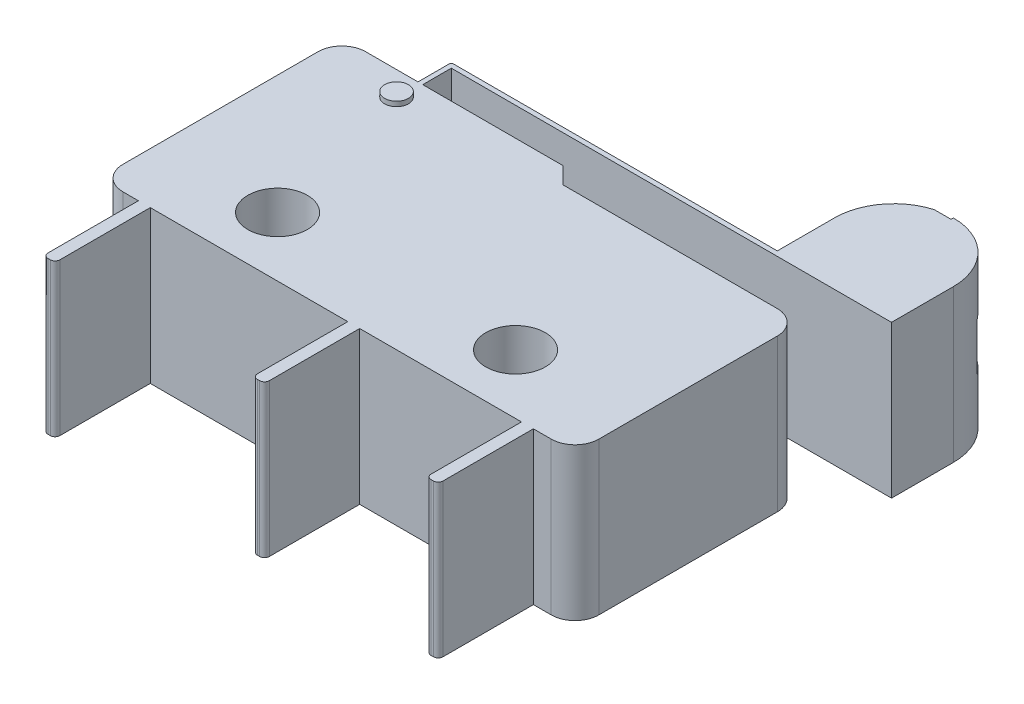
SolidWorks part; units mm, degrees
ref_plane "Front Plane" through (0, 0, 0) normal (0, 0, 1) x (1, 0, 0)
ref_plane "Top Plane" through (0, 0, 0) normal (0, 1, 0) x (1, 0, 0)
ref_plane "Right Plane" through (0, 0, 0) normal (1, 0, 0) x (0, 0, -1)
sketch "Sketch1" plane through (0, 0, 0) normal (0, 1, 0) x (1, 0, 0)
  line L0 (0, 0) -> (20, 0)
  line L1 (0, 0) -> (0, 10.2)
  line L2 (20, 0) -> (20, 9.5)
  line L3 (0, 10.2) -> (9.3, 10.2)
  line L4 (20, 9.5) -> (10, 9.5)
  line L5 (10, 9.5) -> (9.3, 10.2)
  dimension "D1" = 20
  dimension "D2" = 10.2
  dimension "D3" = 9.5
  dimension "D5" = 10
  dimension "D6" = 45
extrude "Boss-Extrude1" add sketch "Sketch1" along normal blind 6.4
fillet "Fillet1" radius 1 4 edges at (0, 3.2, 0) (20, 3.2, 0) (20, 3.2, -9.5) (0, 3.2, -10.2)
sketch "Sketch2" plane through (0, 6.4, 0) normal (0, 1, 0) x (1, 0, 0)
  line L0 (0, 9.2) -> (3.3, 9.2)
  circle A0 centre (3.3, 9.2) radius 0.5
  dimension "D2" = 1
  dimension "D1" = 3.3
extrude "Boss-Extrude2" add sketch "Sketch2" along normal blind 0.2 contours A0 region at (3.3, 6.4, -8.7141)
sketch "Sketch3" plane through (0, 6.4, 0) normal (0, 1, 0) x (1, 0, 0)
  line L0 (3.3, 9.2) -> (3.3, 11.5)
  line L1 (3.3, 0) -> (3.3, 11.5)
  line L2 (1, 0) -> (19, 0) construction
  line L3 (3.3, 11.5) -> (21.9, 11.5)
  line L4 (3.4, 9.2) -> (3.4, 11.5)
  line L5 (3.3, 11.4) -> (21.9, 11.4)
  line L6 (3.2, 9.2) -> (3.2, 11.5)
  line L7 (3.3, 11.6) -> (21.9, 11.6)
  line L8 (3.2, 9.2) -> (3.3874, 9.2)
  line L9 (21.9, 11.6) -> (21.9, 11.4)
  circle A0 centre (3.3, 11.5) radius 0.1
  line M13 (9.3, 10.2) -> (1, 10.2)
  dimension "D1" = 18.6
  dimension "D2" = 11.5
  dimension "D3" = 0.1
  dimension "D4" = 0.1
extrude "Boss-Extrude3" add sketch "Sketch3" against normal up to surface (6.4 mm away) contours A0 L3 L9 L7 | L9 L3 L4 L5 | A0 L5 L4 | L1 A0 L3 | L3 A0 L1 | L5 L0 L4 M13 | A0 L6 L0 M13 region at (3.2859, 6.4, -11.5141) region at (3.35, 6.4, -10.8) region at (3.3777, 6.4, -11.4223) region at (3.2495, 6.4, -10.8109) region at (3.3424, 6.4, -11.4576) region at (12.65, 6.4, -11.45) region at (12.6393, 6.4, -11.55) up to face at (9.93, 0, -5.91)
sketch "Sketch4" plane through (0, 6.4, 0) normal (0, 1, 0) x (1, 0, 0)
  line L0 (21.9, 11.5) -> (16.9, 11.5)
  line L1 (21.9, 11.6) -> (21.9, 11.4) construction
  line L2 (19.4, 11.5) -> (19.4, 16.5)
  line L3 (16.9, 11.5) -> (16.9, 14)
  line L4 (21.9, 11.5) -> (21.9, 14)
  circle A0 centre (19.4, 14) radius 2.5
  line M17 (21.9, 11.6) -> (3.3, 11.6)
  dimension "D1" = 5
  dimension "D2" = 5
extrude "Boss-Extrude4" add sketch "Sketch4" against normal up to surface (6.4 mm away) contours A0 L4 M17 | A0 L2 M17 | L2 A0 M17 | A0 L3 M17 region at (21.4244, 6.4, -12.1496) region at (18.3351, 6.4, -14.0117) region at (20.4649, 6.4, -14.0117) region at (17.3756, 6.4, -12.1496) up to face at (9.387, 0, -8.06)
sketch "Sketch5" plane through (0, 6.4, 0) normal (0, 1, 0) x (1, 0, 0)
  line L0 (0, 0) -> (0, 2.5)
  line L1 (0, 9.2) -> (0, 1) construction
  line L2 (0, 2.5) -> (10, 2.5)
  line L3 (10, 2.5) -> (10, 0)
  circle A0 centre (5, 2.5) radius 1.25
  circle A1 centre (15, 2.5) radius 1.25
  dimension "D2" = 2.5
  dimension "D1" = 2.5
extrude "Cut-Extrude1" cut sketch "Sketch5" against normal through all contours A1 | L2 A0 | L2 A0 region at (5, 6.4, -3.0305) region at (5, 6.4, -1.9695) region at (15, 6.4, -2.5)
sketch "Sketch6" plane through (0, 6.4, 0) normal (0, 1, 0) x (1, 0, 0)
  line L0 (0, 0) -> (0, -4)
  line L1 (2.15, -4) -> (2.15, 0)
  line L2 (1.65, -4) -> (1.65, 0)
  line L3 (1, 0) -> (19, 0) construction
  line L4 (1.65, -4) -> (2.15, -4)
  line L5 (1.65, 0) -> (2.15, 0)
  line L6 (1.65, -4) -> (6.05, -4)
  line L7 (10.95, -4) -> (10.95, 0)
  line L8 (6.05, -4) -> (6.05, -2.8834)
  line L9 (10.45, -4) -> (10.45, 0)
  line L10 (17.75, -4) -> (17.75, 0)
  line L11 (18.25, -4) -> (18.25, 0)
  line L12 (10.45, 0) -> (10.95, 0)
  line L13 (17.75, 0) -> (18.25, 0)
  line L14 (18.25, -4) -> (17.75, -4)
  line L15 (10.95, -4) -> (10.45, -4)
  line M5 (1, 0) -> (19, 0)
  dimension "D1" = 4
  dimension "D2" = 1.65
  dimension "D4" = 8.8
  dimension "D5" = 7.3
  dimension "D3" = 0.5
  dimension "D6" = 0.5
extrude "Boss-Extrude5" add sketch "Sketch6" against normal up to surface (6.4 mm away) contours L2 L4 L1 M5 | L15 L7 L9 M5 | L14 L11 L10 M5 region at (1.9, 6.4, 2) region at (18, 6.4, 2) region at (10.7, 6.4, 2) up to face at (10.1779, 0, -8.8169)
fillet "Fillet2" radius 0.2 6 edges at (18.25, 3.2, 4) (17.75, 3.2, 4) (10.95, 3.2, 4) (10.45, 3.2, 4) (2.15, 3.2, 4) (1.65, 3.2, 4)
sketch "Sketch7" plane through (0, 6.4, 0) normal (0, 1, 0) x (1, 0, 0)
  line L0 (19.4, 16.5) -> (19.4, 16.4)
  line L1 (19.4, 16.4) -> (18.1026, 16.4)
  line L2 (18.1026, 16.4) -> (20.4175, 16.4)
  line L3 (20.4175, 16.4) -> (20.4175, 16.5945)
  line L4 (20.4175, 16.5945) -> (18.1026, 16.5945)
  line L5 (18.1026, 16.5945) -> (18.1026, 16.4)
  arc A0 (21.9, 14) -> (16.9, 14) centre (19.4, 14) ccw construction
  arc M21 (21.9, 14) -> (16.9, 14) centre (19.4, 14) ccw
  dimension "D1" = 0.1
extrude "Cut-Extrude2" cut sketch "Sketch7" against normal blind 10 contours L4 L5 L1 L2 L3 M21 | L1 L0 M21 region at (19.2233, 6.4, -16.5123) region at (19.1368, 6.4, -16.4401)
sketch "Sketch9" plane through (16.9, 0, 0) normal (-1, 0, 0) x (0, 0, 1)
  line L0 (-16.5, 3.2) -> (-15.5, 3.2)
  line L1 (-16.5, 0) -> (-16.5, 6.4) construction
  line L3 (-16.5, 2.2) -> (-15.5, 2.2)
  line L4 (-16.5, 4.2) -> (-15.5, 4.2)
  line L5 (-15.5, 2.2) -> (-15.5, 4.2)
  line L6 (-16.5, 2.2) -> (-16.5, 4.2)
  dimension "D1" = 1
  dimension "D2" = 1
  dimension "D3" = 1
extrude "Cut-Extrude3" cut sketch "Sketch9" against normal through all both and the other way through all contours L6 L0 L5 L4 | L6 L3 L5 L0 region at (16.9, 3.7, -16) region at (16.9, 2.7, -16)
